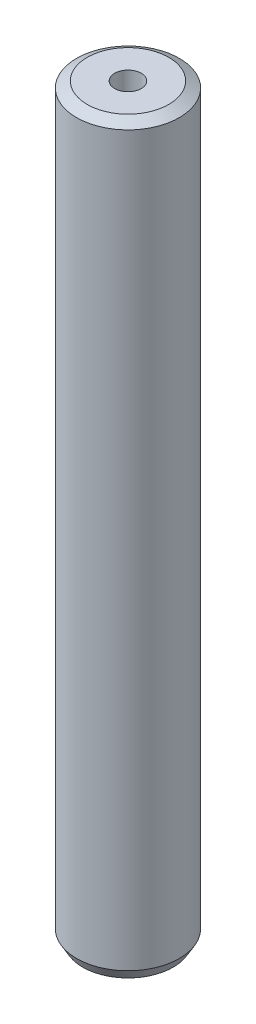
SolidWorks part; units mm, degrees
ref_plane "Front Plane" through (0, 0, 0) normal (0, 0, 1) x (1, 0, 0)
ref_plane "Top Plane" through (0, 0, 0) normal (0, 1, 0) x (1, 0, 0)
ref_plane "Right Plane" through (0, 0, 0) normal (1, 0, 0) x (0, 0, -1)
sketch "Sketch1" plane through (0, 0, 0) normal (0, 1, 0) x (1, 0, 0)
  circle A0 centre (0, 0) radius 12.5
  dimension "SHAFT_OD" = 25
extrude "Boss-Extrude1" add sketch "Sketch1" along normal blind 181.1602
sketch "Sketch2" plane through (0, 0, 0) normal (0, 1, 0) x (1, 0, 0)
  circle A0 centre (0, 0) radius 3.2338
  dimension "BORE_D" = 6.4676
extrude "Cut-Extrude1" cut sketch "Sketch2" along normal through all
chamfer "Chamfer1" distance 1.4885 angle 60 2 edges at (0, 181.1602, 12.5) (0, 0, 12.5) first distance on face at (0, 181.1602, 12.5) first distance on face at (0, 0, 3.2338)
